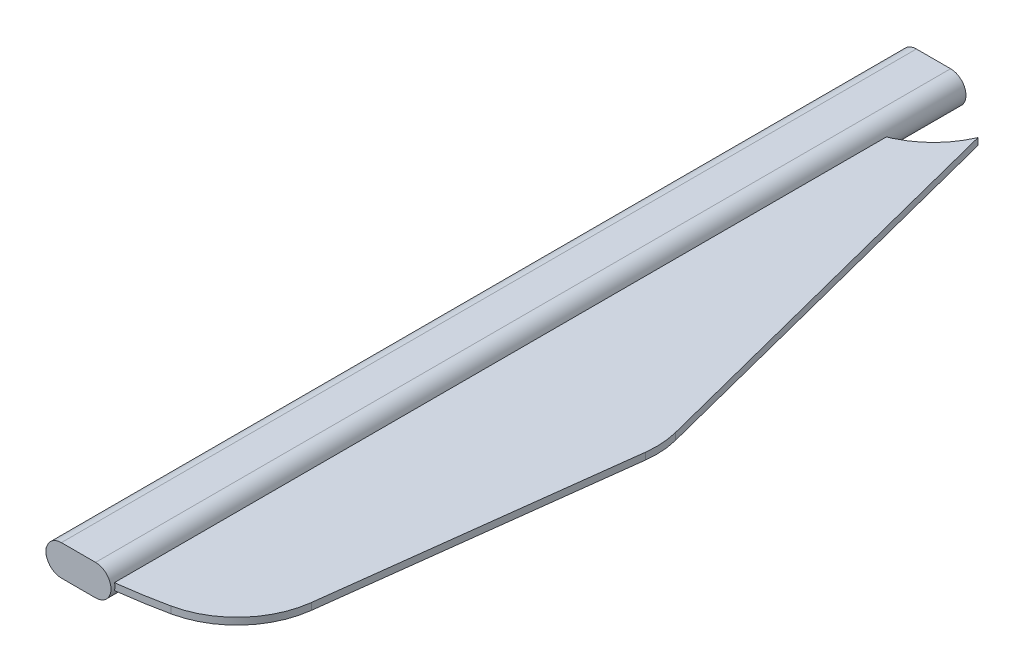
SolidWorks part; units mm, degrees
ref_plane "Front Plane" through (0, 0, 0) normal (0, 0, 1) x (1, 0, 0)
ref_plane "Top Plane" through (0, 0, 0) normal (0, 1, 0) x (1, 0, 0)
ref_plane "Right Plane" through (0, 0, 0) normal (1, 0, 0) x (0, 0, -1)
sketch "Sketch1" plane through (0, 0, 0) normal (0, 0, 1) x (1, 0, 0)
  line L0 (-100, 0) -> (100, 0) construction
  line L1 (-100, 90) -> (100, 90)
  line L2 (-100, -90) -> (100, -90)
  arc A0 (-100, 90) -> (-100, -90) centre (-100, 0) ccw
  arc A1 (100, -90) -> (100, 90) centre (100, 0) ccw
  point P3 (0, 0)
  point P8 (0, 0)
  dimension "D2" = 90
  dimension "D1" = 200
sketch "Sketch2" plane through (0, 0, 0) normal (0, 1, 0) x (1, 0, 0)
  line L0 (0, 0) -> (0, -5000)
  dimension "D1" = 5000
sweep "Sweep1" add profiles "Sketch1" path "Sketch2"
sketch "Sketch3" plane through (0, 0, 0) normal (0, 1, 0) x (1, 0, 0)
  line L13 (100, 0) -> (-100, 0) construction
  line L14 (-190, -462.4932) -> (-190, -5000)
  line L15 (-190, 0) -> (-190, -5000) construction
  line L16 (-190, -5000) -> (-100, -5000) construction
  line L17 (1068.2181, -2578.0796) -> (458.8702, -198.5903)
  line L18 (864.3073, -4502.7496) -> (1080.0447, -2763.6734)
  arc A8 (-190, -462.4932) -> (458.8702, -198.5903) centre (0, 0) ccw
  arc A9 (-190, -5000) -> (472.3184, -4930.2152) centre (-190, -1822.121) ccw
  arc A10 (472.3184, -4930.2152) -> (864.3073, -4502.7496) centre (368.1108, -4441.1949) ccw
  arc A11 (1068.2181, -2578.0796) -> (1080.0447, -2763.6734) centre (583.8481, -2702.1187) cw
  dimension "D1" = 500
extrude "Boss-Extrude1" add sketch "Sketch3" along normal blind 20 and the other way blind 20 separate body
